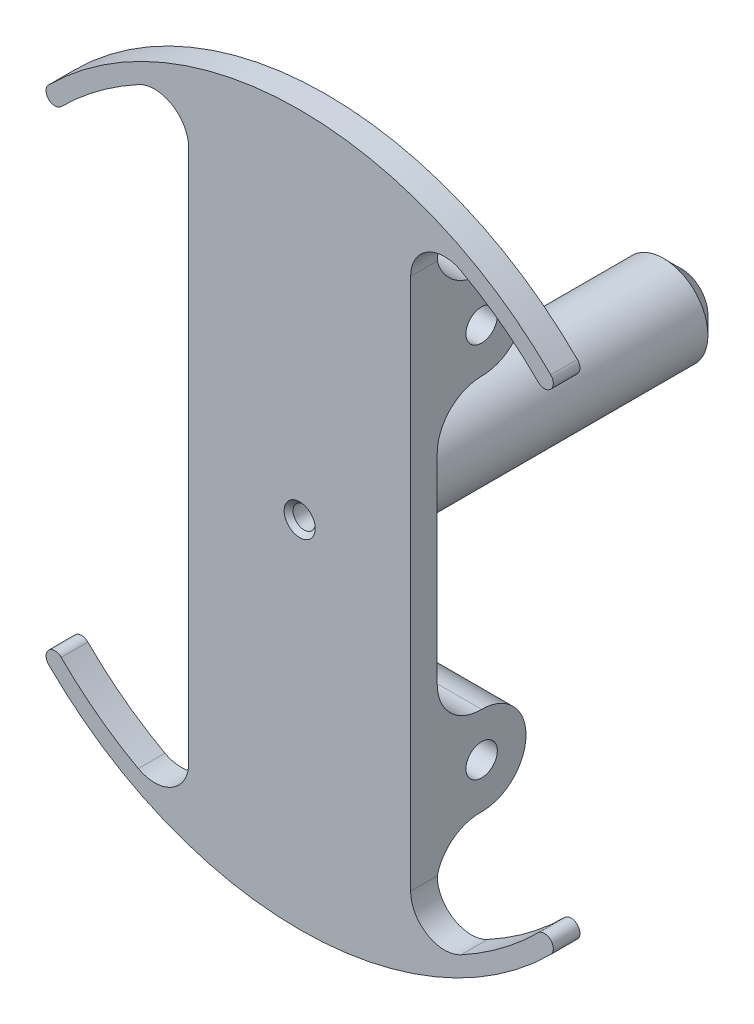
SolidWorks part; units mm, degrees
ref_plane "Front Plane" through (0, 0, 0) normal (0, 0, 1) x (1, 0, 0)
ref_plane "Top Plane" through (0, 0, 0) normal (0, 1, 0) x (1, 0, 0)
ref_plane "Right Plane" through (0, 0, 0) normal (1, 0, 0) x (0, 0, -1)
sketch "Sketch3" plane through (0, 0, 0) normal (0, 0, 1) x (1, 0, 0)
  line L0 (-35.921, -35.921) -> (-34.125, -34.125) construction
  line L1 (-15.875, -38.1) -> (0, -38.1) construction
  line L2 (-15.875, -38.1) -> (-15.875, 38.1)
  line L3 (-15.875, 38.1) -> (0, 38.1) construction
  line L4 (15.875, -38.1) -> (15.875, 38.1)
  line L5 (-15.875, -38.1) -> (15.875, 38.1) construction
  line L6 (-15.875, 38.1) -> (15.875, -38.1) construction
  line L7 (35.921, -35.921) -> (34.125, -34.125) construction
  line L8 (0, -50.8) -> (0, 50.8) construction
  line L9 (0, 38.1) -> (15.875, 38.1) construction
  line L10 (0, -38.1) -> (15.875, -38.1) construction
  line L11 (-34.125, -34.125) -> (-15.875, -15.875) construction
  line L12 (34.125, 34.125) -> (35.921, 35.921) construction
  line L13 (-15.875, -15.875) -> (0, 0) construction
  line L14 (15.875, -15.875) -> (0, 0) construction
  line L15 (-34.125, 34.125) -> (-35.921, 35.921) construction
  line L16 (34.125, -34.125) -> (15.875, -15.875) construction
  line L17 (0, 0) -> (-15.875, 15.875) construction
  line L18 (0, 0) -> (15.875, 15.875) construction
  line L19 (-15.875, 15.875) -> (-34.125, 34.125) construction
  line L20 (15.875, 15.875) -> (34.125, 34.125) construction
  arc A0 (-35.921, -35.921) -> (35.921, -35.921) centre (0, 0) ccw
  arc A1 (-34.125, -34.125) -> (-23.0827, -42.3818) centre (0, 0) ccw
  arc A2 (-15.875, 38.1) -> (-23.0827, 42.3818) centre (-20.7507, 38.1) ccw
  arc A3 (15.875, 38.1) -> (23.0827, 42.3818) centre (20.7507, 38.1) cw
  arc A4 (-15.875, -38.1) -> (-23.0827, -42.3818) centre (-20.7507, -38.1) cw
  arc A5 (15.875, -38.1) -> (23.0827, -42.3818) centre (20.7507, -38.1) ccw
  arc A6 (-35.921, 35.921) -> (-35.921, -35.921) centre (0, 0) ccw construction
  circle A7 centre (0, 0) radius 50.8 construction
  arc A8 (-34.125, 34.125) -> (-34.125, -34.125) centre (0, 0) ccw construction
  circle A9 centre (0, 0) radius 48.26 construction
  arc A10 (34.125, -34.125) -> (34.125, 34.125) centre (0, 0) ccw construction
  arc A11 (34.125, 34.125) -> (23.0827, 42.3818) centre (0, 0) ccw
  arc A12 (35.921, -35.921) -> (35.921, 35.921) centre (0, 0) ccw construction
  arc A13 (35.921, 35.921) -> (-35.921, 35.921) centre (0, 0) ccw
  arc A14 (0, 48.26) -> (-23.0827, 42.3818) centre (0, 0) ccw construction
  arc A15 (-23.0827, 42.3818) -> (-34.125, 34.125) centre (0, 0) ccw
  arc A16 (23.0827, 42.3818) -> (0, 48.26) centre (0, 0) ccw construction
  arc A17 (-23.0827, -42.3818) -> (0, -48.26) centre (0, 0) ccw construction
  arc A18 (23.0827, -42.3818) -> (34.125, -34.125) centre (0, 0) ccw
  arc A19 (0, -48.26) -> (23.0827, -42.3818) centre (0, 0) ccw construction
  arc A20 (-35.921, 35.921) -> (-34.125, 34.125) centre (-35.023, 35.023) ccw
  arc A21 (34.125, 34.125) -> (35.921, 35.921) centre (35.023, 35.023) ccw
  arc A22 (-35.921, -35.921) -> (-34.125, -34.125) centre (-35.023, -35.023) cw
  arc A23 (34.125, -34.125) -> (35.921, -35.921) centre (35.023, -35.023) cw
  point P0 (0, 0)
  point P13 (0, 0)
  point P16 (0, 0)
  point P18 (0, 0)
  dimension "D3" = 2.54
  dimension "D6" = 101.6
  dimension "D1" = 76.2
  dimension "D2" = 31.75
  dimension "D4" = 45
  dimension "D5" = 45
extrude "Boss-Extrude2" add sketch "Sketch3" along normal blind 3.81
sketch "Sketch5" plane through (15.875, 0, 0) normal (1, 0, 0) x (0, 0, -1)
  line L0 (0, 26.9938) -> (0, -26.9938)
  line L1 (0, -38.1) -> (0, 38.1) construction
  line L2 (0, 26.9938) -> (6.35, 26.9939) construction
  line L3 (6.35, 26.9939) -> (6.35, -26.9938) construction
  line L4 (6.35, -26.9938) -> (0, -26.9938) construction
  line L5 (0, 38.1) -> (0, 14.2939)
  line L6 (0, -14.2939) -> (0, -38.1)
  circle A0 centre (-0.0451, 26.9938) radius 0.0451
  arc A2 (6.35, 20.6439) -> (6.3413, 33.3438) centre (6.35, 26.9939) ccw
  arc A3 (6.0778, -33.338) -> (6.2617, -20.6445) centre (6.35, -26.9938) ccw
  arc A4 (6.35, 20.6439) -> (0, 14.2939) centre (6.3675, 14.2763) ccw
  arc A5 (6.3413, 33.3438) -> (0, 38.1) centre (6.1542, 39.6999) cw
  arc A6 (6.35, -20.6438) -> (0, -14.2939) centre (6.2623, -14.3815) cw
  arc A7 (6.35, -33.3439) -> (0, -38.1) centre (6.0797, -39.6) ccw
  arc A8 (6.3413, 33.3438) -> (0, 26.9938) centre (6.35, 26.9939) ccw construction
  arc A9 (0, 26.9938) -> (6.35, 20.6439) centre (6.35, 26.9939) ccw construction
  arc A10 (6.2617, -20.6445) -> (0, -26.9938) centre (6.35, -26.9938) ccw construction
  arc A11 (0, -26.9938) -> (6.0778, -33.338) centre (6.35, -26.9938) ccw construction
  point P5 (0, 0)
  line M6 (0, -38.1) -> (0, 38.1)
  dimension "D1" = 53.9877
  dimension "D2" = 6.35
  dimension "D3" = 12.7
  dimension "D4" = 12.7
extrude "Boss-Extrude4" add sketch "Sketch5" against normal up to surface (31.75 mm away) contours A2 A5 L0 A4 M6 | A7 A3 A6 L6 M6 region at (15.875, 26.931, -5.3159) region at (15.875, -26.9385, -5.3244) up to face at (-15.875, 0, 1.905)
hole_wizard "#8 Clearance Hole1" positions "Sketch8" profile "Sketch7" hole size "#8" standard "ANSI Inch" end condition through all
sketch "Sketch8" plane through (15.875, 0, 0) normal (1, 0, 0) x (0, 0, -1)
  point P7 (6.35, 26.9939)
  point P10 (6.35, -26.8934)
sketch "Sketch7" plane through (15.875, 26.9939, -6.35) normal (0, 1, 0) x (0, 0, -1)
  line L0 (0, 0) -> (0, 52.168)
  line L1 (0, 52.168) -> (2.2479, 52.168)
  line L2 (2.2479, 52.168) -> (2.2479, 0)
  line L5 (2.2479, 0) -> (0, 0)
  line L11 (0, -6.35) -> (0, 107.95) construction
  dimension "Thru Hole Dia." = 4.4958
  dimension "Thru Hole Depth" = 52.168
hole_wizard "1/8 (0.125) Diameter Hole1" positions "Sketch9" profile "Sketch10" hole size "1/8" standard "ANSI Inch" end condition up to next
sketch "Sketch9" plane through (0, 0, 0) normal (0, 0, -1) x (-1, 0, 0)
  point P0 (0, 0)
sketch "Sketch10" plane through (0, 0, 0) normal (1, 0, 0) x (0, 1, 0)
  line L0 (0, 0) -> (0, 3.81)
  line L1 (0, 3.81) -> (2.2225, 3.81)
  line L2 (1.5875, 3.175) -> (1.5875, 0.635)
  line L3 (1.5875, 0.635) -> (2.2225, 0)
  line L5 (2.2225, 0) -> (0, 0)
  line L6 (-1.5875, 0.635) -> (-2.2225, 0) construction
  line L7 (2.2225, 3.81) -> (1.5875, 3.175)
  line L8 (-2.2225, 3.81) -> (-1.5875, 3.175) construction
  line L11 (0, -6.35) -> (0, 107.95) construction
  dimension "Thru Hole Dia." = 3.175
  dimension "Thru Hole Depth" = 3.81
  dimension "Near C'Sink Dia." = 4.445
  dimension "Near C'Sink Angle" = 90
  dimension "Far C'Sink Dia." = 4.445
  dimension "Far C'Sink Angle" = 90
sketch "Sketch11" plane through (0, 0, 3.81) normal (0, 0, 1) x (1, 0, 0)
  circle A0 centre (0, 0) radius 6.35
  circle A1 centre (0, 0) radius 2.2225
  dimension "D1" = 4.445
  dimension "D2" = 12.7
extrude "Boss-Extrude5" add sketch "Sketch11" against normal blind 50.8 from surface starting at face at (-2.2225, 0, 0)
chamfer "Chamfer1" distance 2.54 angle 45 1 edges at (-6.35, 0, -50.8)
chamfer "Chamfer2" distance 1.27 angle 45 1 edges at (-2.2225, 0, -50.8)
chamfer "Chamfer3" distance 5.08 angle 45 1 edges at (-6.35, 0, 0)
